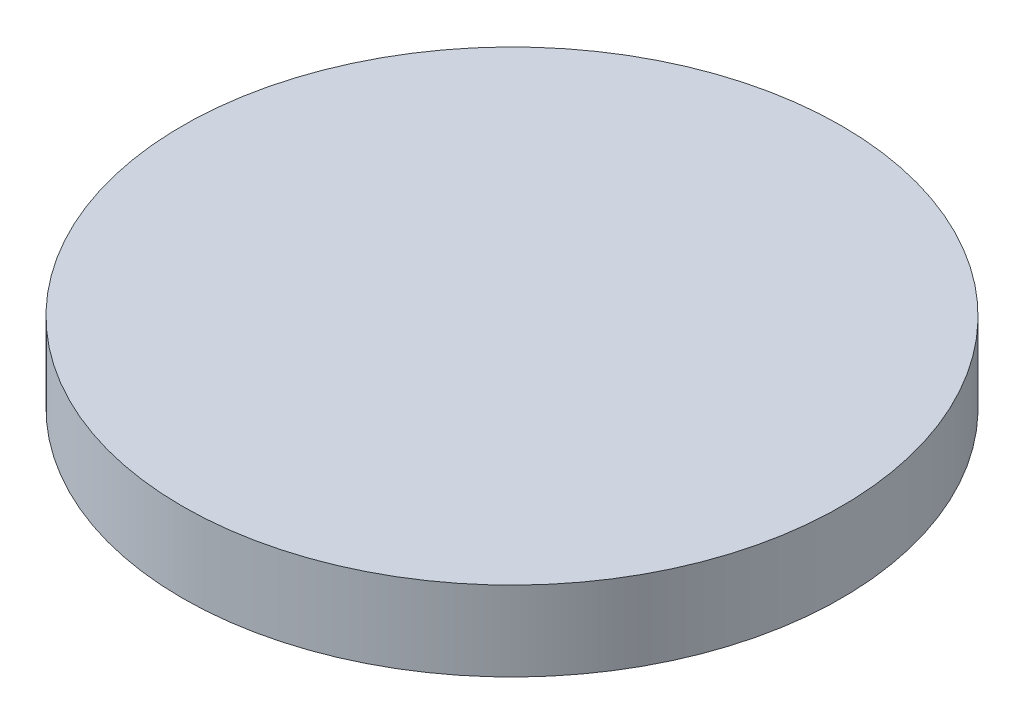
SolidWorks part; units mm, degrees
material "PTFE (general)"
ref_plane "Front Plane" through (0, 0, 0) normal (0, 0, 1) x (1, 0, 0)
ref_plane "Top Plane" through (0, 0, 0) normal (0, 1, 0) x (1, 0, 0)
ref_plane "Right Plane" through (0, 0, 0) normal (1, 0, 0) x (0, 0, -1)
sketch "Sketch1" plane through (0, 0, 0) normal (0, 1, 0) x (1, 0, 0)
  circle A0 centre (0, 0) radius 8.28
  dimension "D1" = 16.56
extrude "Boss-Extrude1" add sketch "Sketch1" along normal blind 2
